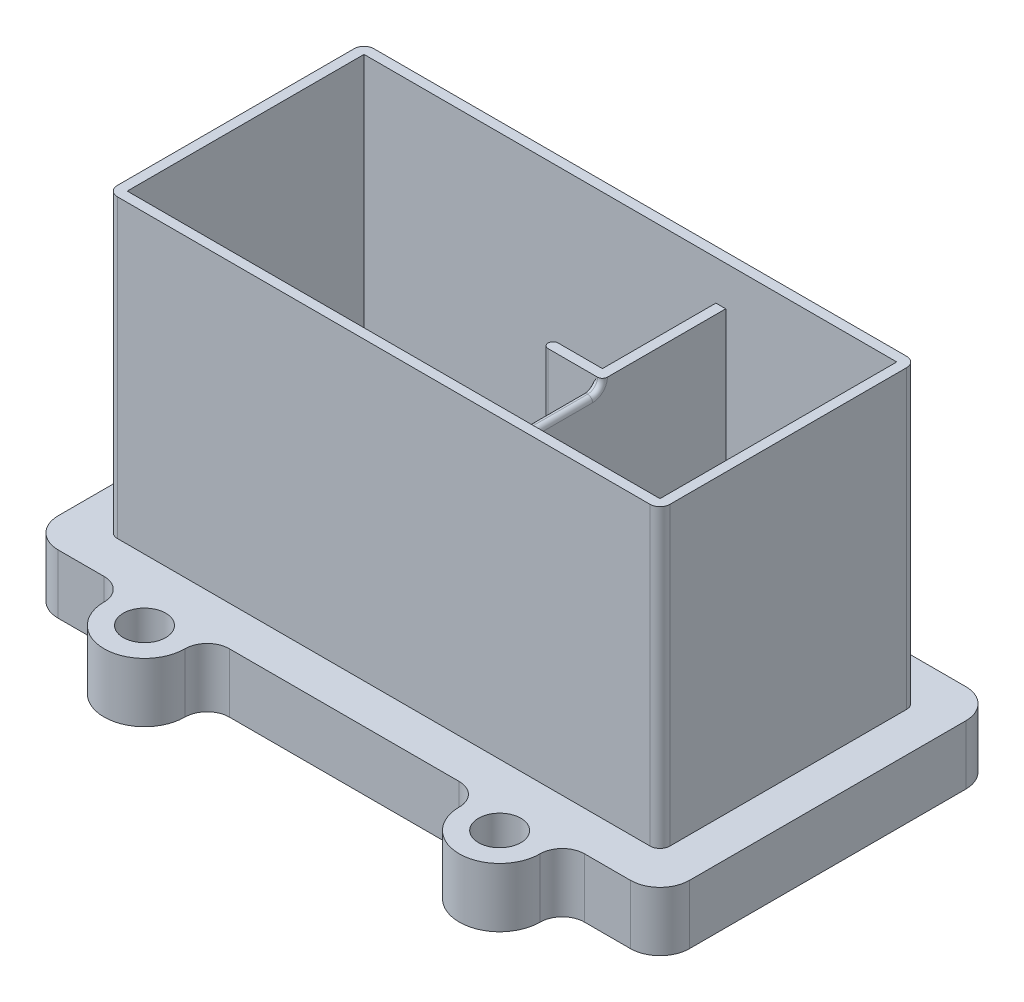
SolidWorks part; units mm, degrees
ref_plane "Front Plane" through (0, 0, 0) normal (0, 0, 1) x (1, 0, 0)
ref_plane "Top Plane" through (0, 0, 0) normal (0, 1, 0) x (1, 0, 0)
ref_plane "Right Plane" through (0, 0, 0) normal (1, 0, 0) x (0, 0, -1)
sketch "Base-plate and ports" plane through (0, 0, 0) normal (0, 1, 0) x (1, 0, 0)
  line L5 (-16, -7) -> (-16, 7)
  line L10 (-15, -7) -> (-15, 7)
  line L11 (-14.5, 7.5) -> (14.5, 7.5)
  line L12 (15, -7) -> (15, 7)
  line L13 (-14.5, -7.5) -> (14.5, -7.5)
  line L14 (16, -7) -> (16, 7)
  line L16 (-14.5, -8.5) -> (14.5, -8.5) construction
  line L17 (-14.5, 8.5) -> (14.5, 8.5) construction
  line L18 (-14.5, 8.5) -> (-3.175, 8.5)
  line L20 (3.175, 8.5) -> (14.5, 8.5)
  line L21 (12.175, -8.5) -> (14.5, -8.5)
  line L22 (5.825, -8.5) -> (-5.825, -8.5)
  line L23 (-12.175, -8.5) -> (-14.5, -8.5)
  circle A33 centre (-10.5, 3) radius 0.35
  circle A34 centre (0, 3) radius 0.35
  circle A35 centre (10.5, 3) radius 0.35
  circle A36 centre (0, -3) radius 0.35
  circle A37 centre (10.5, -3) radius 0.35
  circle A38 centre (-10.5, -3) radius 0.35
  arc A41 (-15, -7) -> (-14.5, -7.5) centre (-14.5, -7) ccw
  arc A42 (14.5, -7.5) -> (15, -7) centre (14.5, -7) ccw
  arc A43 (15, 7) -> (14.5, 7.5) centre (14.5, 7) ccw
  arc A44 (-14.5, 7.5) -> (-15, 7) centre (-14.5, 7) ccw
  circle A45 centre (0, 9.625) radius 1.075
  circle A46 centre (-9, -9.625) radius 1.075
  circle A47 centre (9, -9.625) radius 1.075
  arc A48 (-14.5, 8.5) -> (-16, 7) centre (-14.5, 7) ccw
  arc A49 (16, 7) -> (14.5, 8.5) centre (14.5, 7) ccw
  arc A50 (14.5, -8.5) -> (16, -7) centre (14.5, -7) ccw
  arc A51 (-16, -7) -> (-14.5, -8.5) centre (-14.5, -7) ccw
  arc A52 (-11.05, -9.625) -> (-6.95, -9.625) centre (-9, -9.625) ccw
  arc A53 (6.95, -9.625) -> (11.05, -9.625) centre (9, -9.625) ccw
  arc A54 (-2.05, 9.625) -> (2.05, 9.625) centre (0, 9.625) cw
  arc A55 (-11.05, -9.625) -> (-12.175, -8.5) centre (-12.175, -9.625) ccw
  arc A56 (-6.95, -9.625) -> (-5.825, -8.5) centre (-5.825, -9.625) cw
  arc A57 (6.95, -9.625) -> (5.825, -8.5) centre (5.825, -9.625) ccw
  arc A58 (11.05, -9.625) -> (12.175, -8.5) centre (12.175, -9.625) cw
  arc A59 (2.05, 9.625) -> (3.175, 8.5) centre (3.175, 9.625) ccw
  arc A60 (-2.05, 9.625) -> (-3.175, 8.5) centre (-3.175, 9.625) cw
  point P2 (-15, -7.5)
  point P5 (0, 7.5)
  point P10 (15, 7.5)
  point P16 (-15, 7.5)
  point P17 (-15, 0)
  dimension "D7" = 30
  dimension "D3" = 6
  dimension "D8" = 10.5
  dimension "D9" = 0.5
  dimension "D10" = 0.7
  dimension "D18" = 1
  dimension "D19" = 4.1
  dimension "D5" = 4.5
  dimension "D12" = 2.125
  dimension "D13" = 2.125
  dimension "D11" = 2.15
  dimension "D2" = 4.5
  dimension "D6" = 10.5
  dimension "D4" = 15
  dimension "D16" = 2
  dimension "D17" = 18
  dimension "D14" = 6
  dimension "D15" = 3
extrude "Base plate and ports" add sketch "Base-plate and ports" along normal mid plane 3 contours L13 L10 L11 L12 | L10 L13 L12 L11 A38 A37 A36 A35 A34 A33 | A34 | A36 region at (-15.6039, 0, 0) region at (0, 0, 0) region at (0, 0, -3) region at (0, 0, 3)
sketch "Reservoirs" plane through (0, 1.5, 0) normal (0, 1, 0) x (1, 0, 0)
  line L0 (-15, -7) -> (-15, 7) construction
  line L1 (-13.5, -6.5) -> (13.5, -6.5)
  line L2 (-14, -6) -> (-14, 6)
  line L3 (-13.5, 6.5) -> (13.5, 6.5)
  line L4 (14, -6) -> (14, 6)
  line L5 (-14, -6.5) -> (14, 6.5) construction
  line L6 (-14, 6.5) -> (14, -6.5) construction
  line L7 (-14.5, 7.5) -> (14.5, 7.5) construction
  line L8 (-4.3333, -6) -> (4.3333, -6)
  line L9 (-13.5, -6) -> (-4.8333, -6)
  line L10 (-13.5, -6) -> (-13.5, 6)
  line L11 (-13.5, 6) -> (-4.8333, 6)
  line L12 (-4.8333, -6) -> (-4.8333, 6)
  line L13 (-13.5, -6) -> (-4.8333, 6) construction
  line L14 (-13.5, 6) -> (-4.8333, -6) construction
  line L15 (-4.3333, -6) -> (-4.3333, 6)
  line L16 (-4.3333, 6) -> (4.3333, 6)
  line L17 (4.3333, -6) -> (4.3333, 6)
  line L18 (-4.3333, -6) -> (4.3333, 6) construction
  line L19 (-4.3333, 6) -> (4.3333, -6) construction
  line L20 (4.8333, -6) -> (13.5, -6)
  line L21 (4.8333, -6) -> (4.8333, 6)
  line L22 (4.8333, 6) -> (13.5, 6)
  line L23 (13.5, -6) -> (13.5, 6)
  line L24 (4.8333, -6) -> (13.5, 6) construction
  line L25 (4.8333, 6) -> (13.5, -6) construction
  line L26 (-4.8333, 6) -> (-4.3333, 6)
  line L27 (-4.8333, -6) -> (-4.3333, -6)
  line L28 (4.3333, 6) -> (4.8333, 6)
  line L29 (4.3333, -6) -> (4.8333, -6)
  arc A0 (-14, -6) -> (-13.5, -6.5) centre (-13.5, -6) ccw
  arc A1 (13.5, -6.5) -> (14, -6) centre (13.5, -6) ccw
  arc A2 (14, 6) -> (13.5, 6.5) centre (13.5, 6) ccw
  arc A3 (-13.5, 6.5) -> (-14, 6) centre (-13.5, 6) ccw
  point P0 (0, 0)
  point P10 (-9.1667, 0)
  point P16 (9.1667, 0)
  point P18 (0, 0)
  dimension "D10" = 0.5
  dimension "D1" = 1
  dimension "D2" = 1
  dimension "D3" = 0.5
  dimension "D4" = 0.5
  dimension "D5" = 0.5
  dimension "D6" = 0.5
  dimension "D7" = 0.5
  dimension "D8" = 0.5
  dimension "D9" = 0.5
extrude "Boss-Extrude1" add sketch "Reservoirs" along normal blind 15 contours L3 A3 L2 A0 L1 A1 L4 A2 L23 L20 L21 L22 L27 L9 L10 L11 L26 L16 L17 L8 region at (-13.6353, 1.5, 6.1353)
extrude "Boss-Extrude5" add sketch "Reservoirs<4>" along normal offset from surface (13 mm away) 2 contours L17 L29 L21 L28 region at (4.5833, 1.5, 0) up to face at (0, 16.5, 0)
sketch "Reservoirs<4>" plane through (0, 1.5, 0) normal (0, 1, 0) x (1, 0, 0) same geometry as "Reservoirs"
sketch "Sketch3" plane through (0, 0, 0) normal (0, 1, 0) x (1, 0, 0)
  line L0 (-13.5, -6) -> (-13.5, 6) construction
  line L1 (-13.5, 0.25) -> (4.3333, 0.25)
  line L2 (-13.5, 0.25) -> (-13.5, -0.25)
  line L3 (-13.5, -0.25) -> (4.3333, -0.25)
  line L4 (4.3333, 0.25) -> (4.3333, -0.25)
  line L5 (4.3333, -6) -> (4.3333, 6) construction
  line L6 (1.8333, 0.25) -> (1.8333, -0.25)
  point P8 (-13.5, 0)
  dimension "D1" = 0.5
  dimension "D2" = 2.5
extrude "Boss-Extrude3" add sketch "Sketch3" along normal blind 3 from surface contours L6 L1 L2 L3 | L1 L6 L3 L4 region at (-5.8333, 0, 0) region at (3.0833, 0, 0) starting at face at (-4.5833, 1.5, 0)
sketch "Sketch4" plane through (0, 0, 0.25) normal (0, 0, 1) x (1, 0, 0)
  line L0 (-10.5, 4.5) -> (1.3333, 4.5) construction
  line L1 (-10.5, 5) -> (1.3333, 5)
  line L2 (-10.5, 4) -> (1.3333, 4)
  line L3 (-10.5, 5) -> (-13.5, 5)
  line L5 (-13.5, 1.5) -> (-4.8333, 1.5) construction
  line L6 (-13.5, 16.5) -> (-13.5, 1.5) construction
  line L7 (-13.5, 5) -> (-13.5, 4)
  line L8 (-13.5, 4) -> (-10.5, 4)
  line L9 (-4.8333, 1.5) -> (-4.3333, 1.5) construction
  arc A0 (-10.5, 5) -> (-10.5, 4) centre (-10.5, 4.5) ccw
  arc A1 (1.3333, 4) -> (1.3333, 5) centre (1.3333, 4.5) ccw
  point P2 (-4.5833, 4.5)
  point P11 (1.8333, 4.5)
  point P20 (-4.5833, 1.5)
  line M6 (-13.5, 4.5) -> (-13.5, 1.5)
  line M10 (4.3333, 4.5) -> (-13.5, 4.5)
  dimension "D1" = 1
  dimension "D3" = 3
extrude "Cut-Extrude1" cut sketch "Sketch4" against normal up to next contours A0 L3 L7 M10 | A1 L1 A0 M10 | A0 L8 M10 M6 | L2 A1 A0 M10 region at (-12.194, 4.7557, 0.25) region at (-4.5833, 4.7476, 0.25) region at (-4.5833, 4.2524, 0.25) region at (-12.194, 4.2443, 0.25)
extrude "Boss-Extrude6" add sketch "Sketch3<4>" along normal up to surface (14.5 mm away) contours L1 L6 L3 L4 region at (3.0833, 0, 0) up to face at (4.5833, 14.5, 0)
sketch "Sketch3<4>" plane through (0, 0, 0) normal (0, 1, 0) x (1, 0, 0) same geometry as "Sketch3"
fillet "Fillet1" [suppressed] radius 1
sketch "Sketch5" plane through (4.8333, 0, 0) normal (1, 0, 0) x (0, 0, -1)
  line L0 (-5.5, 14.5) -> (-0.75, 14.5) construction
  line L3 (-6, 14.5) -> (6, 14.5) construction
  line L4 (-5.5, 15) -> (-0.75, 15)
  line L5 (-6, 14.5) -> (-6, 16.5)
  line L6 (-5.5, 14) -> (-0.75, 14)
  line L9 (-6, 16.5) -> (6, 16.5) construction
  line L11 (-6, 16.5) -> (-0.25, 16.5)
  line L12 (-0.25, 16.5) -> (-0.25, 14.5)
  arc A4 (-5.5, 15) -> (-5.5, 14) centre (-5.5, 14.5) ccw
  arc A5 (-0.75, 14) -> (-0.75, 15) centre (-0.75, 14.5) ccw
  point P2 (-3.125, 14.5)
  line M38 (6, 14.5) -> (-6, 14.5)
  dimension "D2" = 1
extrude "Cut-Extrude2" cut sketch "Sketch5" against normal up to surface (0.5 mm away) from surface contours L6 A5 A4 M38 | A5 L4 A4 M38 | A5 L12 L11 L5 A4 L4 region at (4.8333, 15.7394, 3.125) region at (4.8333, 14.7446, 3.125) region at (4.8333, 14.2554, 3.125) up to face at (4.3333, 8, 3.125) starting at face at (4.8333, 8, 0)
fillet "Fillet2" radius 0.25 12 edges at (4.8333, 14.1464, 5.8536) (4.8333, 14.1464, 0.3964) (4.3333, 14.1464, 5.8536) (4.3333, 14.1464, 0.3964) (4.8333, 14, 3.125) (4.3333, 14, 3.125) (1.8333, 9.5, 0.25) (1.6869, 4.1464, 0.25) (1.8333, 9.5, -0.25) (1.6869, 4.1464, -0.25) (-6.0833, 4, 0.25) (-6.0833, 4, -0.25)
